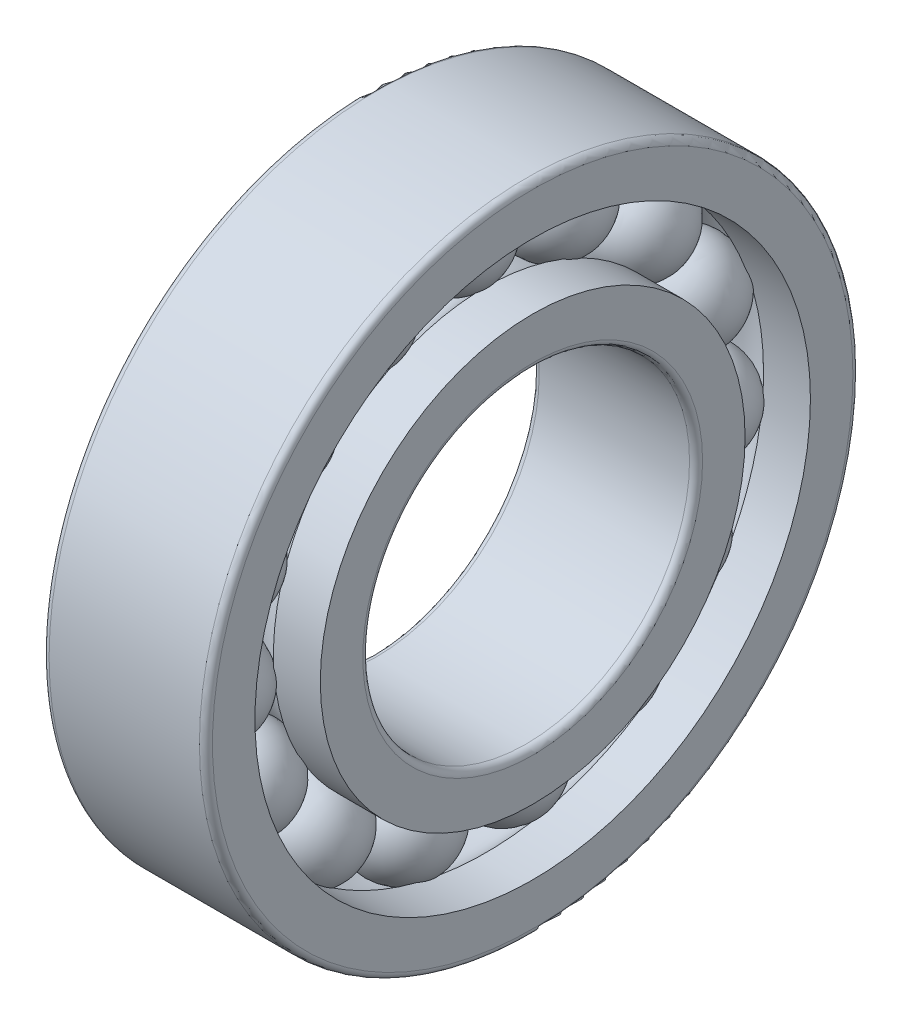
SolidWorks part; units mm, degrees
ref_plane "Plane1" through (0, 0, 0) normal (0, 0, 1) x (1, 0, 0)
ref_plane "Plane2" through (0, 0, 0) normal (0, 1, 0) x (1, 0, 0)
ref_plane "Plane3" through (0, 0, 0) normal (1, 0, 0) x (0, 0, -1)
sketch "Clipboard" plane through (0, 0, 0) normal (0, 0, 1) x (1, 0, 0)
  line L0 (-10, 0) -> (10, 0) construction
  line L1 (0, 0) -> (21.5988, -5.7874)
  line L2 (0, 0) -> (4.7618, -0.0831)
  line L3 (0, 0) -> (22.3573, 0.3902)
  line L4 (0, 0) -> (-22.3573, -0.3902)
  dimension "BallCLRad" = 4.7625
  dimension "Count" = 359
  dimension "Show_count" = 359
  dimension "Max_count" = 15
  dimension "Min_count" = 1
sketch "CagSpiSke" plane through (0, 0, 0) normal (0, 0, 1) x (1, 0, 0)
  line L0 (0.0952, 4.6038) -> (0.0953, 4.9213)
  line L1 (0.0953, 4.9213) -> (-0.0953, 4.9213)
  line L2 (-0.0953, 4.9213) -> (-0.0952, 4.6038)
  line L3 (-0.0952, 4.6038) -> (0.0952, 4.6038)
  line L4 (-20.6375, 0) -> (20.6375, 0) construction
  line L5 (0, 0) -> (0, 23.7692) construction
  dimension "Thickness" = 0.1905
  dimension "OD" = 9.8425
  dimension "ID" = 9.2075
revolve "CageSpine" add sketch "CagSpiSke" angle 0.001 about L4 reverse direction yes
ref_axis "Axis1" through (-50, 0, 0) along (1, 0, 0)
sketch "CagBalSke" plane through (0, 0, 0) normal (0, 0, 1) x (1, 0, 0)
  line L0 (-1.0478, 4.7625) -> (1.0478, 4.7625)
  line L1 (-1.905, 4.7625) -> (1.905, 4.7625) construction
  line L2 (-10, 0) -> (10, 0) construction
  line L3 (0, 0) -> (0, 24) construction
  arc A0 (1.0478, 4.7625) -> (-1.0478, 4.7625) centre (0, 4.7625) cw
  dimension "CageWallOD" = 2.0955
  dimension "BallCLRad" = 4.7625
revolve "CageBall" [suppressed] add sketch "CagBalSke" angle 360 about L1 reverse direction yes
pattern_circular "CageBalls" [suppressed] count 15 every 24 about axis through (-50, 0, 0) along (1, 0, 0)
sketch "CagTrmODSke" plane through (0, 0, 0) normal (0, 0, 1) x (1, 0, 0)
  line L0 (1.0488, 4.9212) -> (1.0488, 5.8113)
  line L1 (1.0488, 5.8113) -> (-1.0488, 5.8113)
  line L2 (-1.0488, 5.8113) -> (-1.0488, 4.9212)
  line L3 (-1.0488, 4.9212) -> (1.0488, 4.9212)
  line L4 (-20.6375, 0) -> (20.6375, 0) construction
  line L5 (0, 0) -> (0, 25) construction
  dimension "Width" = 2.0975
  dimension "ID" = 9.8425
  dimension "OD" = 11.6225
revolve "CageTrimOD" [suppressed] cut sketch "CagTrmODSke" angle 360 about L4 reverse direction yes
sketch "CagTrmIDSke" plane through (0, 0, 0) normal (0, 0, 1) x (1, 0, 0)
  line L0 (1.0487, 3.7158) -> (1.0488, 4.6037)
  line L1 (1.0488, 4.6037) -> (-1.0488, 4.6037)
  line L2 (-1.0488, 4.6037) -> (-1.0487, 3.7158)
  line L3 (-1.0487, 3.7158) -> (1.0487, 3.7158)
  line L4 (-20.6375, 0) -> (20.6375, 0) construction
  line L5 (0, 0) -> (0, 25) construction
  dimension "ID" = 7.4315
  dimension "OD" = 9.2075
  dimension "Width" = 2.0975
revolve "CageTrimID" [suppressed] cut sketch "CagTrmIDSke" angle 360 about L4 reverse direction yes
sketch "BalSimSke" plane through (0, 0, 0) normal (0, 0, 1) x (1, 0, 0)
  line L0 (-10, 0) -> (10, 0) construction
  line L1 (-10, 4.7625) -> (10, 4.7625) construction
  line L2 (0, 0) -> (0, 23) construction
  circle A0 centre (0, 4.7625) radius 0.9525
  dimension "Ball_diameter" = 1.905
  dimension "BallCLRad" = 4.7625
revolve "BallsSimplified" [suppressed] add sketch "BalSimSke" angle 360 about L0
sketch "BalDetSke" plane through (0, 0, 0) normal (0, 0, 1) x (1, 0, 0)
  line L0 (-0.9525, 4.7625) -> (0.9525, 4.7625)
  line L1 (-1.905, 4.7625) -> (1.905, 4.7625) construction
  line L2 (0, 0) -> (0, 25) construction
  arc A0 (0.9525, 4.7625) -> (-0.9525, 4.7625) centre (0, 4.7625) cw
  dimension "Ball_diameter" = 1.905
  dimension "BallCLRad" = 4.7625
revolve "BallDetailed" add sketch "BalDetSke" angle 360 about L1 reverse direction yes
sketch "InnRacSke" plane through (0, 0, 0) normal (0, 0, 1) x (1, 0, 0)
  line L0 (-0.676, 4.1275) -> (-1.5875, 4.1275)
  line L1 (-1.5875, 4.1275) -> (-1.5875, 3.302)
  line L2 (-1.4605, 3.175) -> (1.4605, 3.175)
  line L3 (1.5875, 3.302) -> (1.5875, 4.1275)
  line L4 (1.5875, 4.1275) -> (0.676, 4.1275)
  line L5 (-20.6375, 0) -> (20.6375, 0) construction
  line L6 (0, 0) -> (0, 30) construction
  arc A0 (-1.5875, 3.302) -> (-1.4605, 3.175) centre (-1.4605, 3.302) ccw
  arc A1 (1.4605, 3.175) -> (1.5875, 3.302) centre (1.4605, 3.302) ccw
  arc A2 (0.676, 4.1275) -> (-0.676, 4.1275) centre (0, 4.7625) cw
  dimension "Fillet_radius" = 0.127
  dimension "Ball_diameter" = 1.855
  dimension "ID" = 6.35
  dimension "OD" = 8.255
  dimension "Width" = 3.175
  dimension "BallCLRad" = 4.7625
revolve "InnerRace" add sketch "InnRacSke" angle 360 about L5 reverse direction yes
sketch "OutRacSke" plane through (0, 0, 0) normal (0, 0, 1) x (1, 0, 0)
  line L0 (-0.676, 5.3975) -> (-1.5875, 5.3975)
  line L1 (-1.5875, 5.3975) -> (-1.5875, 6.223)
  line L2 (-1.4605, 6.35) -> (1.4605, 6.35)
  line L3 (1.5875, 6.223) -> (1.5875, 5.3975)
  line L4 (1.5875, 5.3975) -> (0.676, 5.3975)
  line L5 (-20.6375, 0) -> (20.6375, 0) construction
  line L6 (0, 0) -> (0, 30) construction
  arc A0 (-1.5875, 6.223) -> (-1.4605, 6.35) centre (-1.4605, 6.223) cw
  arc A1 (1.4605, 6.35) -> (1.5875, 6.223) centre (1.4605, 6.223) cw
  arc A2 (0.676, 5.3975) -> (-0.676, 5.3975) centre (0, 4.7625) ccw
  dimension "Fillet_radius" = 0.127
  dimension "Ball_diameter" = 1.855
  dimension "OD" = 12.7
  dimension "ID" = 10.795
  dimension "Width" = 3.175
  dimension "BallCLRad" = 4.7625
revolve "OuterRace" add sketch "OutRacSke" angle 360 about L5 reverse direction yes
pattern_circular "BallsDetailed" count 15 every 24 about axis through (-50, 0, 0) along (1, 0, 0) of "BallDetailed"
equation "\"BallCLRad@Clipboard\" = ( \"OD@OutRacSke\" + \"ID@InnRacSke\" ) / 4"
equation "\"BallCLRad@BalSimSke\" = \"BallCLRad@Clipboard\""
equation "\"BallCLRad@BalDetSke\" = \"BallCLRad@Clipboard\""
equation "\"BallCLRad@InnRacSke\" = \"BallCLRad@Clipboard\""
equation "\"BallCLRad@OutRacSke\" = \"BallCLRad@Clipboard\""
equation "\"Ball_diameter@InnRacSke\" = \"Ball_diameter@BalDetSke\" - 0.05"
equation "\"Ball_diameter@OutRacSke\" = \"Ball_diameter@BalDetSke\" - 0.05"
equation "\"Ball_diameter@BalSimSke\" = \"Ball_diameter@BalDetSke\""
equation "\"Width@OutRacSke\" = \"Width@InnRacSke\""
equation "\"Fillet_radius@OutRacSke\" = \"Fillet_radius@InnRacSke\""
equation "\"Max_count@Clipboard\" = int( 3.14159265 / atn(( \"Ball_diameter@BalDetSke\" / 2) / sqr( \"BallCLRad@Clipboard\"  *  \"BallCLRad@Clipboard\" - ( \"Ball_diameter@BalDetSke\" / 2) *  ( \"Ball_diameter@BalDetSke\" / 2))))"
equation "\"Max_count@Clipboard\" = ((sgn( \"Max_count@Clipboard\" - \"Count@Clipboard\" )-1)*( \"Max_count@Clipboard\" - \"Count@Clipboard\" ))/-2+ \"Count@Clipboard\""
equation "\"Count@BallsDetailed\" = int( \"Show_count@Clipboard\" ) "
equation "\"Count@BallsDetailed\" = ((sgn( \"Count@BallsDetailed\" - \"Max_count@Clipboard\" )-1)*( \"Count@BallsDetailed\" - \"Max_count@Clipboard\" ))/-2+ \"Max_count@Clipboard\""
equation "\"Count@BallsDetailed\" = ((sgn( \"Count@BallsDetailed\" - \"Min_count@Clipboard\" )+1)*( \"Count@BallsDetailed\" - \"Min_count@Clipboard\"))/2 +\"Min_count@Clipboard\""
equation "\"Angle@BallsDetailed\" = 360.0 / \"Max_count@Clipboard\""
equation "\"BallCLRad@CagBalSke\" = \"BallCLRad@Clipboard\""
equation "\"Count@CageBalls\" = \"Count@BallsDetailed\""
equation "\"Angle@CageBalls\" = \"Angle@BallsDetailed\""
equation "\"Angle@CageSpine\" =  \"Angle@CageBalls\" * ( \"Count@CageBalls\" -1 + int( \"Count@CageBalls\" / \"Max_count@Clipboard\" ) )  + 0.001 -  int( \"Count@CageBalls\" / \"Max_count@Clipboard\" ) * 0.001"
equation "\"Angle@CageSpine\" =  \"Angle@CageSpine\" * int( \"Min_count@Clipboard\" / 2) + int(1 / \"Min_count@Clipboard\")  * 0.001"
equation "\"CageWallOD@CagBalSke\" =  \"Ball_diameter@BalDetSke\" * 1.1"
equation "\"Thickness@CagSpiSke\" =  \"Ball_diameter@BalDetSke\" * 0.1"
equation "\"OD@CagTrmODSke\" = \"BallCLRad@Clipboard\" * 2 + \"CageWallOD@CagBalSke\" + 0.002"
equation "\"ID@CagTrmODSke\" = \"BallCLRad@Clipboard\" * 2 + \"Ball_diameter@BalDetSke\" / 6"
equation "\"OD@CagTrmIDSke\" = \"BallCLRad@Clipboard\" * 2 - \"Ball_diameter@BalDetSke\" / 6"
equation "\"ID@CagTrmIDSke\" = \"BallCLRad@Clipboard\" * 2 - \"CageWallOD@CagBalSke\" + 0.002"
equation "\"OD@CagSpiSke\" = \"ID@CagTrmODSke\""
equation "\"ID@CagSpiSke\" = \"OD@CagTrmIDSke\""
equation "\"Width@CagTrmODSke\" = \"CageWallOD@CagBalSke\" + 0.002"
equation "\"Width@CagTrmIDSke\" = \"CageWallOD@CagBalSke\" + 0.002"
